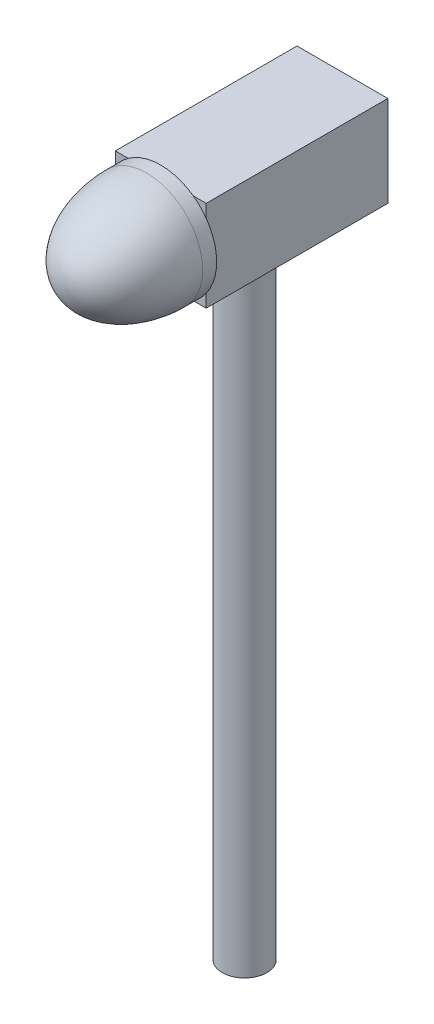
SolidWorks part; units mm, degrees
material "PVC Rigid"
ref_plane "Front Plane" through (0, 0, 0) normal (0, 0, 1) x (1, 0, 0)
ref_plane "Top Plane" through (0, 0, 0) normal (0, 1, 0) x (1, 0, 0)
ref_plane "Right Plane" through (0, 0, 0) normal (1, 0, 0) x (0, 0, -1)
sketch "Sketch1" plane through (0, 0, 0) normal (0, 1, 0) x (1, 0, 0)
  circle A0 centre (0, 0) radius 16
  dimension "D1" = 32
extrude "Boss-Extrude1" add sketch "Sketch1" along normal blind 450
sketch "Sketch2" plane through (0, 450, 0) normal (0, 1, 0) x (1, 0, 0)
  line L1 (-32.5, -60) -> (32.5, -60)
  line L2 (-32.5, -60) -> (-32.5, 70)
  line L3 (-32.5, 70) -> (32.5, 70)
  line L4 (32.5, -60) -> (32.5, 70)
  point P0 (0, 0)
  dimension "D1" = 130
  dimension "D2" = 65
  dimension "D3" = 60
  dimension "D4" = 32.5
extrude "Boss-Extrude2" add sketch "Sketch2" along normal blind 65
sketch "Sketch3" plane through (0, 0, 60) normal (0, 0, 1) x (1, 0, 0)
  line L0 (-32.5, 450) -> (32.5, 450) construction
  line L1 (32.5, 515) -> (32.5, 450) construction
  circle A0 centre (0, 482.5) radius 40
  dimension "D3" = 80
  dimension "D1" = 32.5
  dimension "D2" = 32.5
extrude "Boss-Extrude3" add sketch "Sketch3" along normal blind 10 contours A0
dome "Dome1" faces to dome 1 distance 60 reverse direction no elliptical dome yes face at (40, 482.5, 70) parameters "D1"=60
